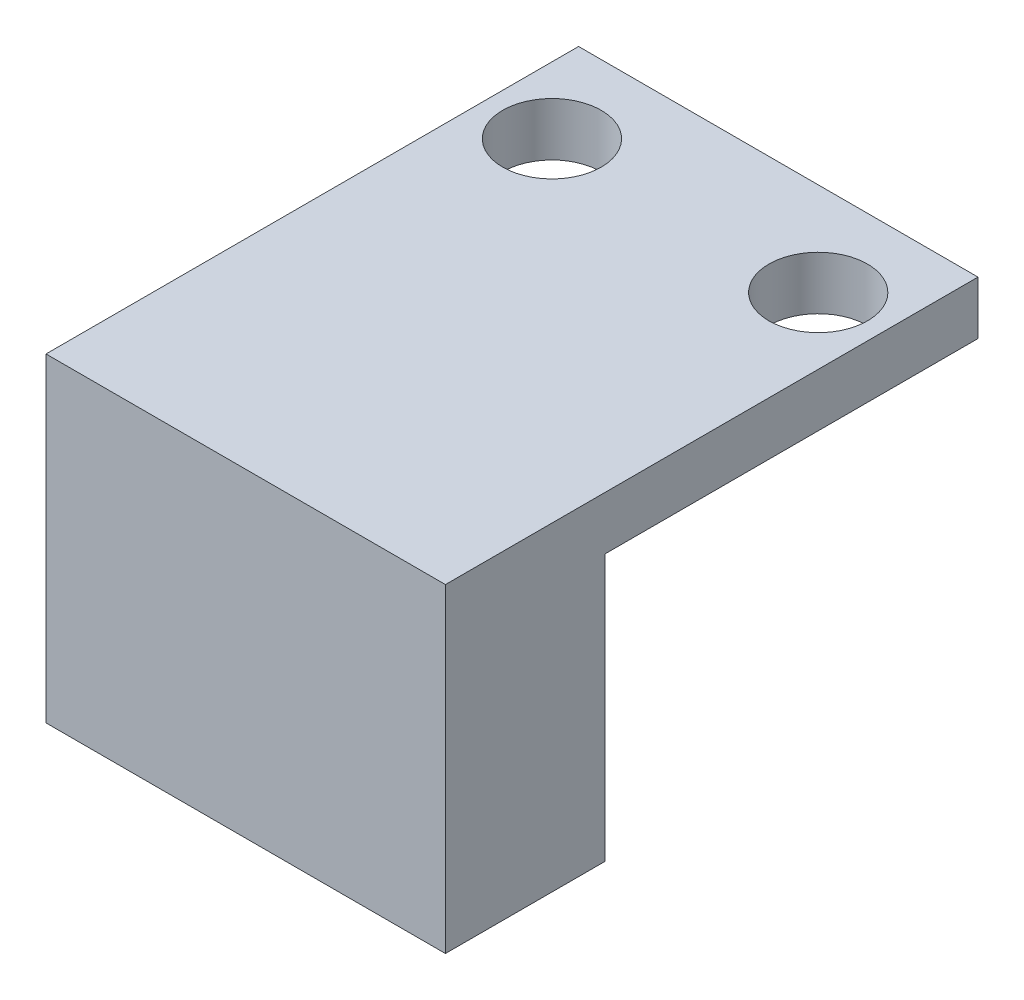
SolidWorks part; units mm, degrees
ref_plane "Front Plane" through (0, 0, 0) normal (0, 0, 1) x (1, 0, 0)
ref_plane "Top Plane" through (0, 0, 0) normal (0, 1, 0) x (1, 0, 0)
ref_plane "Right Plane" through (0, 0, 0) normal (1, 0, 0) x (0, 0, -1)
sketch "Sketch1" plane through (0, 0, 0) normal (0, 1, 0) x (1, 0, 0)
  line L0 (-5, 0) -> (5, 0) construction
  line L1 (-7.5, 3.5) -> (7.5, 3.5)
  line L2 (-7.5, 3.5) -> (-7.5, -16.5)
  line L3 (-7.5, -16.5) -> (7.5, -16.5)
  line L4 (7.5, 3.5) -> (7.5, -16.5)
  circle A0 centre (-5, 0) radius 1.85
  circle A1 centre (5, 0) radius 1.85
  point P8 (0, 0)
  point P9 (0, 3.5)
  dimension "D3" = 3.7
  dimension "D1" = 10
  dimension "D2" = 15
  dimension "D4" = 20
  dimension "D5" = 3.5
extrude "Boss-Extrude1" add sketch "Sketch1" along normal blind 2
sketch "Sketch2" plane through (0, 0, 0) normal (0, -1, 0) x (1, 0, 0)
  line L1 (-7.5, 16.5) -> (7.5, 16.5)
  line L2 (-7.5, 16.5) -> (-7.5, 10.5)
  line L3 (-7.5, 10.5) -> (7.5, 10.5)
  line L4 (-7.5, 16.5) -> (-7.5, -3.5)
  line L5 (-7.5, -3.5) -> (7.5, -3.5)
  line L6 (7.5, -3.5) -> (7.5, 16.5)
  line L7 (7.5, 16.5) -> (-7.5, 16.5)
  line L8 (-7.5, 16.5) -> (-7.5, -3.5)
  line L9 (-7.5, -3.5) -> (7.5, -3.5)
  line L10 (7.5, -3.5) -> (7.5, 16.5)
  line L11 (7.5, 16.5) -> (-7.5, 16.5)
  line L12 (7.5, 16.5) -> (7.5, 10.5)
  line M7 (-7.5, 16.5) -> (-7.5, -3.5)
  line M9 (7.5, -3.5) -> (7.5, 16.5)
  line M10 (7.5, 16.5) -> (-7.5, 16.5)
  dimension "D2" = 6
  dimension "D1" = 0
extrude "Boss-Extrude2" add sketch "Sketch2" along normal blind 10 contours L3 M7 M9 M10 region at (0, 0, 13.5)
